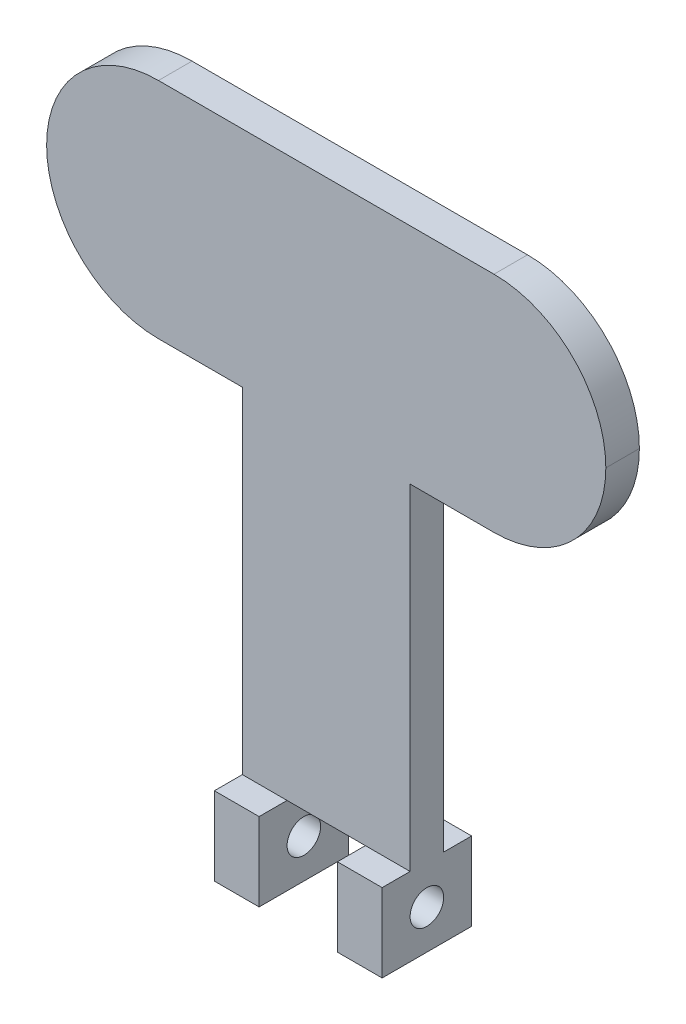
SolidWorks part; units mm, degrees
ref_plane "前视基准面" through (0, 0, 0) normal (0, 0, 1) x (1, 0, 0)
ref_plane "上视基准面" through (0, 0, 0) normal (0, 1, 0) x (1, 0, 0)
ref_plane "右视基准面" through (0, 0, 0) normal (1, 0, 0) x (0, 0, -1)
sketch "草图1" plane through (0, 0, 0) normal (0, 0, 1) x (1, 0, 0)
  line L1 (-25, -10) -> (25, -10)
  line L2 (-25, -10) -> (-25, 10)
  line L3 (-25, 10) -> (25, 10)
  line L4 (25, -10) -> (25, 10)
  line L5 (-25, -10) -> (25, 10) construction
  line L6 (-25, 10) -> (25, -10) construction
  point P0 (0, 0)
  dimension "D1" = 50
  dimension "D2" = 20
extrude "凸台-拉伸1" add sketch "草图1" along normal blind 3
fillet "圆角1" radius 10 1 edges at (25, 10, 1.5)
fillet "圆角2" radius 10 1 edges at (-25, 10, 1.5)
fillet "圆角3" radius 10 3 edges at (25, -5, 3) (25, -5, 0) (25, -10, 1.5)
fillet "圆角4" radius 10 3 edges at (-25, -5, 0) (-25, -5, 3) (-25, -10, 1.5)
sketch "草图2" plane through (0, 0, 0) normal (0, 0, -1) x (-1, 0, 0)
  line L0 (15, -10) -> (-15, -10) construction
  line L1 (-7.5, -40) -> (7.5, -40)
  line L2 (-7.5, -40) -> (-7.5, -10)
  line L3 (-7.5, -10) -> (7.5, -10)
  line L4 (7.5, -40) -> (7.5, -10)
  line L5 (-7.5, -40) -> (7.5, -10) construction
  line L6 (-7.5, -10) -> (7.5, -40) construction
  point P0 (0, -25)
  dimension "D1" = 15
  dimension "D2" = 30
extrude "凸台-拉伸2" add sketch "草图2" against normal blind 3
sketch "草图4" plane through (0, -40, 0) normal (0, -1, 0) x (-1, 0, 0)
  line L0 (-7.5, 0) -> (7.5, 0) construction
  line L1 (-3.5, -5.5) -> (-7.5, -5.5)
  line L2 (-3.5, -5.5) -> (-3.5, 2.5)
  line L3 (-3.5, 2.5) -> (-7.5, 2.5)
  line L4 (-7.5, -5.5) -> (-7.5, 2.5)
  line L5 (-3.5, -5.5) -> (-7.5, 2.5) construction
  line L6 (-3.5, 2.5) -> (-7.5, -5.5) construction
  line L7 (3.5, -5.5) -> (7.5, -5.5)
  line L8 (3.5, -5.5) -> (3.5, 2.5)
  line L9 (3.5, 2.5) -> (7.5, 2.5)
  line L10 (7.5, -5.5) -> (7.5, 2.5)
  line L11 (3.5, -5.5) -> (7.5, 2.5) construction
  line L12 (3.5, 2.5) -> (7.5, -5.5) construction
  point P0 (-5.5, -1.5)
  point P5 (5.5, -1.5)
  dimension "D1" = 4
  dimension "D2" = 4
  dimension "D3" = 8
  dimension "D4" = 8
  dimension "D5" = 2.5
  dimension "D6" = 2.5
extrude "凸台-拉伸4" add sketch "草图4" along normal blind 7
sketch "草图5" plane through (7.5, 0, 0) normal (1, 0, 0) x (0, 0, -1)
  line L0 (2.5, -40) -> (0, -40) construction
  circle A0 centre (-1.5, -43.5) radius 1.5
  dimension "D1" = 3
  dimension "D2" = 3.5
extrude "切除-拉伸1" cut sketch "草图5" against normal through all
